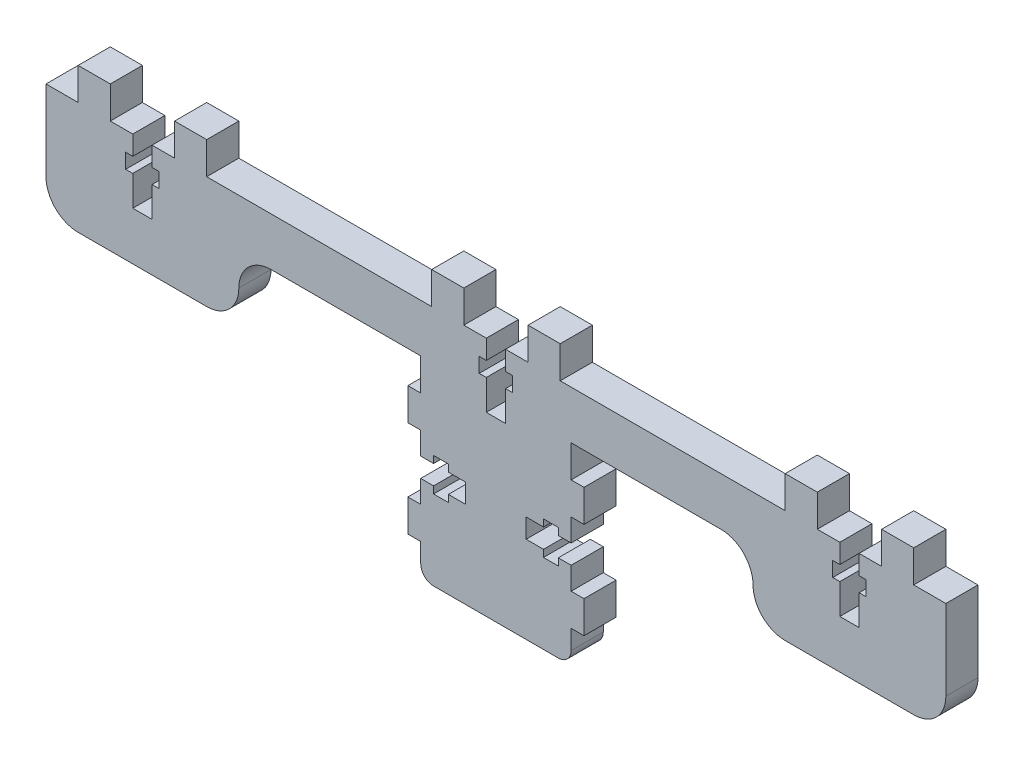
SolidWorks part; units mm, degrees
ref_plane "Plan de face" through (0, 0, 0) normal (0, 0, 1) x (1, 0, 0)
ref_plane "Plan de dessus" through (0, 0, 0) normal (0, 1, 0) x (1, 0, 0)
ref_plane "Plan de droite" through (0, 0, 0) normal (1, 0, 0) x (0, 0, -1)
sketch "Esquisse1" plane through (0, 0, 0) normal (0, 0, 1) x (1, 0, 0)
  line L0 (0, 0) -> (0, 37.5) construction
  line L1 (0, 37.5) -> (23.4, 37.5) construction
  line L2 (23.4, 37.5) -> (23.4, 0) construction
  line L3 (23.4, 0) -> (0, 0) construction
  line L4 (0, 15) -> (25.4472, 15) construction
  line L5 (23.4, 25) -> (23.4, 30)
  line L6 (23.4, 30) -> (51.7, 30)
  line L7 (51.7, 30) -> (51.7, 20)
  line L8 (51.7, 20) -> (81.7, 20)
  line L9 (23.4, 5) -> (23.4, 0)
  line L10 (0, 0) -> (23.4, 0)
  line L11 (11.7, 37.5) -> (11.7, 0) construction
  line L12 (0, 0) -> (0, 5)
  line L13 (81.7, 20) -> (81.7, 37.5)
  line L14 (81.7, 37.5) -> (-58.3, 37.5) construction
  line L15 (-58.3, 20) -> (-58.3, 37.5)
  line L16 (-28.3, 20) -> (-58.3, 20)
  line L17 (-28.3, 30) -> (-28.3, 20)
  line L18 (0, 30) -> (-28.3, 30)
  line L19 (0, 25) -> (0, 30)
  line L20 (-58.3, 37.5) -> (-53.3, 37.5)
  line L21 (-33.3, 37.5) -> (56.7, 37.5) construction
  line L22 (76.7, 37.5) -> (81.7, 37.5)
  line L23 (1.7, 37.5) -> (-33.3, 37.5)
  line L24 (21.7, 37.5) -> (56.7, 37.5)
  point P19 (11.7, 37.5)
  line B0 (23.3419, 15) -> (9.4468, 15) construction
  line B1 (23.4, 13.5) -> (23.4, 10)
  line B2 (25.4, 10) -> (25.4, 5)
  line B3 (25.4, 5) -> (23.4, 5)
  line B4 (25.4, 10) -> (23.4, 10)
  line B5 (23.4, 16.2928) -> (23.4, 20)
  line B6 (23.4, 20) -> (25.4, 20)
  line B7 (25.4, 20) -> (25.4, 25)
  line B8 (25.4, 25) -> (23.4, 25)
  line B9 (23.4, 13.5) -> (23.4, 16.5) construction
  line B10 (23.4, 16.5) -> (21.4, 16.5)
  line B11 (19.1, 16.5) -> (19.1, 17.6)
  line B12 (21.4, 12.4) -> (19.1, 12.4)
  line B13 (21.4, 17.6) -> (21.4, 16.5)
  line B14 (19.1, 16.5) -> (16.4, 16.5)
  line B15 (16.4, 16.5) -> (16.4, 13.5)
  line B16 (16.4, 13.5) -> (19.1, 13.5)
  line B17 (21.4, 13.5) -> (21.4, 12.4)
  line B18 (19.1, 17.6) -> (21.4, 17.6)
  line B19 (19.1, 12.4) -> (19.1, 13.5)
  line B20 (21.4, 13.5) -> (23.4, 13.5)
  line B21 (16.4, 15) -> (23.4, 15) construction
  line B22 (0.0581, 15) -> (13.9532, 15) construction
  line B23 (0, 13.5) -> (0, 10)
  line B24 (-2, 10) -> (-2, 5)
  line B25 (-2, 5) -> (0, 5)
  line B26 (-2, 10) -> (0, 10)
  line B27 (0, 16.2928) -> (0, 20)
  line B28 (0, 20) -> (-2, 20)
  line B29 (-2, 20) -> (-2, 25)
  line B30 (-2, 25) -> (0, 25)
  line B31 (0, 13.5) -> (0, 16.5) construction
  line B32 (0, 16.5) -> (2, 16.5)
  line B33 (4.3, 16.5) -> (4.3, 17.6)
  line B34 (2, 12.4) -> (4.3, 12.4)
  line B35 (2, 17.6) -> (2, 16.5)
  line B36 (4.3, 16.5) -> (7, 16.5)
  line B37 (7, 16.5) -> (7, 13.5)
  line B38 (7, 13.5) -> (4.3, 13.5)
  line B39 (2, 13.5) -> (2, 12.4)
  line B40 (4.3, 17.6) -> (2, 17.6)
  line B41 (4.3, 12.4) -> (4.3, 13.5)
  line B42 (2, 13.5) -> (0, 13.5)
  line B43 (7, 15) -> (0, 15) construction
  line B44 (69.3, 34.5) -> (69.3, 32.2)
  line B45 (65.2, 32.2) -> (65.2, 27.5)
  line B46 (68.2, 27.5) -> (68.2, 32.2)
  line B47 (69.3, 32.2) -> (68.2, 32.2)
  line B48 (66.7, 37.5) -> (66.7, 26.2792) construction
  line B49 (68.2, 37.5) -> (71.7, 37.5)
  line B50 (71.7, 42.5) -> (76.7, 42.5)
  line B51 (76.7, 42.5) -> (76.7, 37.5)
  line B52 (71.7, 42.5) -> (71.7, 37.5)
  line B53 (65.2, 37.5) -> (61.7, 37.5)
  line B54 (61.7, 37.5) -> (61.7, 42.5)
  line B55 (61.7, 42.5) -> (56.7, 42.5)
  line B56 (56.7, 42.5) -> (56.7, 37.5)
  line B57 (68.2, 37.5) -> (65.2, 37.5) construction
  line B58 (65.2, 37.5) -> (65.2, 34.5)
  line B59 (65.2, 32.2) -> (64.1, 32.2)
  line B60 (64.1, 34.5) -> (65.2, 34.5)
  line B61 (65.2, 27.5) -> (68.2, 27.5)
  line B62 (68.2, 34.5) -> (69.3, 34.5)
  line B63 (64.1, 32.2) -> (64.1, 34.5)
  line B64 (68.2, 34.5) -> (68.2, 37.5)
  line B65 (66.7, 27.5) -> (66.7, 37.5) construction
  line B66 (-45.9, 34.5) -> (-45.9, 32.2)
  line B67 (-41.8, 32.2) -> (-41.8, 27.5)
  line B68 (-44.8, 27.5) -> (-44.8, 32.2)
  line B69 (-45.9, 32.2) -> (-44.8, 32.2)
  line B70 (-43.3, 37.5) -> (-43.3, 26.2792) construction
  line B71 (-44.8, 37.5) -> (-48.3, 37.5)
  line B72 (-48.3, 42.5) -> (-53.3, 42.5)
  line B73 (-53.3, 42.5) -> (-53.3, 37.5)
  line B74 (-48.3, 42.5) -> (-48.3, 37.5)
  line B75 (-41.8, 37.5) -> (-38.3, 37.5)
  line B76 (-38.3, 37.5) -> (-38.3, 42.5)
  line B77 (-38.3, 42.5) -> (-33.3, 42.5)
  line B78 (-33.3, 42.5) -> (-33.3, 37.5)
  line B79 (-44.8, 37.5) -> (-41.8, 37.5) construction
  line B80 (-41.8, 37.5) -> (-41.8, 34.5)
  line B81 (-41.8, 32.2) -> (-40.7, 32.2)
  line B82 (-40.7, 34.5) -> (-41.8, 34.5)
  line B83 (-41.8, 27.5) -> (-44.8, 27.5)
  line B84 (-44.8, 34.5) -> (-45.9, 34.5)
  line B85 (-40.7, 32.2) -> (-40.7, 34.5)
  line B86 (-44.8, 34.5) -> (-44.8, 37.5)
  line B87 (-43.3, 27.5) -> (-43.3, 37.5) construction
  line B88 (14.3, 34.5) -> (14.3, 32.2)
  line B89 (10.2, 32.2) -> (10.2, 27.5)
  line B90 (13.2, 27.5) -> (13.2, 32.2)
  line B91 (14.3, 32.2) -> (13.2, 32.2)
  line B92 (11.7, 37.5) -> (11.7, 26.2792) construction
  line B93 (13.2, 37.5) -> (16.7, 37.5)
  line B94 (16.7, 42.5) -> (21.7, 42.5)
  line B95 (21.7, 42.5) -> (21.7, 37.5)
  line B96 (16.7, 42.5) -> (16.7, 37.5)
  line B97 (10.2, 37.5) -> (6.7, 37.5)
  line B98 (6.7, 37.5) -> (6.7, 42.5)
  line B99 (6.7, 42.5) -> (1.7, 42.5)
  line B100 (1.7, 42.5) -> (1.7, 37.5)
  line B101 (13.2, 37.5) -> (10.2, 37.5) construction
  line B102 (10.2, 37.5) -> (10.2, 34.5)
  line B103 (10.2, 32.2) -> (9.1, 32.2)
  line B104 (9.1, 34.5) -> (10.2, 34.5)
  line B105 (10.2, 27.5) -> (13.2, 27.5)
  line B106 (13.2, 34.5) -> (14.3, 34.5)
  line B107 (9.1, 32.2) -> (9.1, 34.5)
  line B108 (13.2, 34.5) -> (13.2, 37.5)
  line B109 (11.7, 27.5) -> (11.7, 37.5) construction
  dimension "D1" = 23.4
  dimension "D2" = 7.5
  dimension "D3" = 15
  dimension "D4" = 22.5
  dimension "D5" = 10
  dimension "D6" = 30
  dimension "D7" = 55
sketch_block_instance "Bloc1-1"
sketch_block "Bloc1" parameters "D1"=10, "D2"=5, "D3"=2
sketch_block_instance "Bloc3-3"
sketch_block "Bloc3" parameters "D1"=5.2, "D2"=3, "D3"=2.3, "D4"=2, "D5"=7
sketch_block_instance "Bloc1-3"
sketch_block_instance "Insert M3 plots ep 5mm-14"
sketch_block "Insert M3 plots ep 5mm" parameters "D1"=10, "D2"=5, "D3"=5
sketch_block_instance "Decoupe Insert M3-4"
sketch_block "Decoupe Insert M3" parameters "D1"=5.2, "D2"=3, "D3"=2.3, "D4"=3, "D5"=10
sketch_block_instance "Insert M3 plots ep 5mm-15"
sketch_block_instance "Insert M3 plots ep 5mm-16"
extrude "Boss.-Extru.1" add sketch "Esquisse1" along normal blind 5 contours B39 B42 B23 B26 B24 B25 L9 B3 B2 B4 B1 B20 B17 B12 B19 B16 B15 B14 B11 B18 B13 B10 B5 B6 B7 B8 region at (11.7, 26.5671, 0)
fillet "Congé1" radius 5 6 edges at (-28.3, 30, 2.5) (-58.3, 20, 2.5) (-28.3, 20, 2.5) (81.7, 20, 2.5) (51.7, 20, 2.5) (51.7, 30, 2.5)
fillet "Fillet1" radius 2 2 edges at (0, 0, 2.5) (23.4, 0, 2.5)
